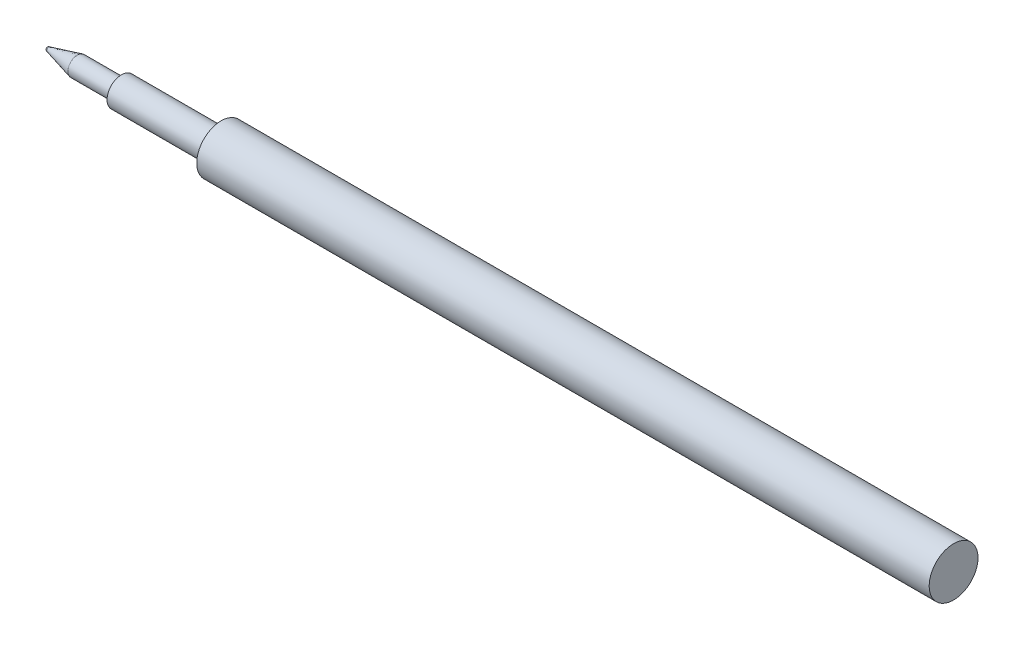
SolidWorks part; units mm, degrees
material "PP Film"
ref_plane "Front Plane" through (0, 0, 0) normal (0, 0, 1) x (1, 0, 0)
ref_plane "Top Plane" through (0, 0, 0) normal (0, 1, 0) x (1, 0, 0)
ref_plane "Right Plane" through (0, 0, 0) normal (1, 0, 0) x (0, 0, -1)
sketch "Sketch1" plane through (0, 0, 0) normal (0, 0, 1) x (1, 0, 0)
  line L0 (-90, 0) -> (-102.25, 0)
  line L1 (0, 0) -> (-90, 0)
  line L2 (0, 0) -> (0, 3)
  line L3 (0, 3) -> (-90, 3)
  line L4 (-90, 0) -> (-90, 3)
  line L5 (-102.25, 0) -> (-102.25, 1.77)
  line L6 (-102.25, 1.77) -> (-90, 1.77)
  line L7 (-102.25, 0) -> (-94.74, 0)
  line L10 (-94.74, 0) -> (-100.74, 0)
  line L13 (-100.74, 0) -> (-107.67, 0)
  line L14 (-107.67, 0) -> (-107.67, 1.16)
  line L15 (-107.67, 1.16) -> (-102.25, 1.16)
  line L16 (-107.67, 1.16) -> (-111.17, 0.25)
  line L17 (-111.17, 0.25) -> (-111.17, 0)
  line L18 (-111.17, 0) -> (-107.67, 0)
  line L19 (-111.17, 0) -> (-111.42, 0)
  arc A0 (-111.42, 0) -> (-111.17, 0.25) centre (-111.17, 0) cw
  dimension "D1" = 3
  dimension "D2" = 90
  dimension "D3" = 1.77
  dimension "D4" = 12.25
  dimension "D8" = 1.16
  dimension "D9" = 5.42
  dimension "D10" = 3.5
  dimension "D11" = 0.25
  dimension "D12" = 0.25
revolve "Revolve1" add sketch "Sketch1" angle 360 about L1 region at (-45, 1.5, 0) region at (-96.125, 0.885, 0) region at (-104.96, 0.58, 0) region at (-109.0435, 0.4014, 0) region at (-111.2761, 0.1061, 0)
